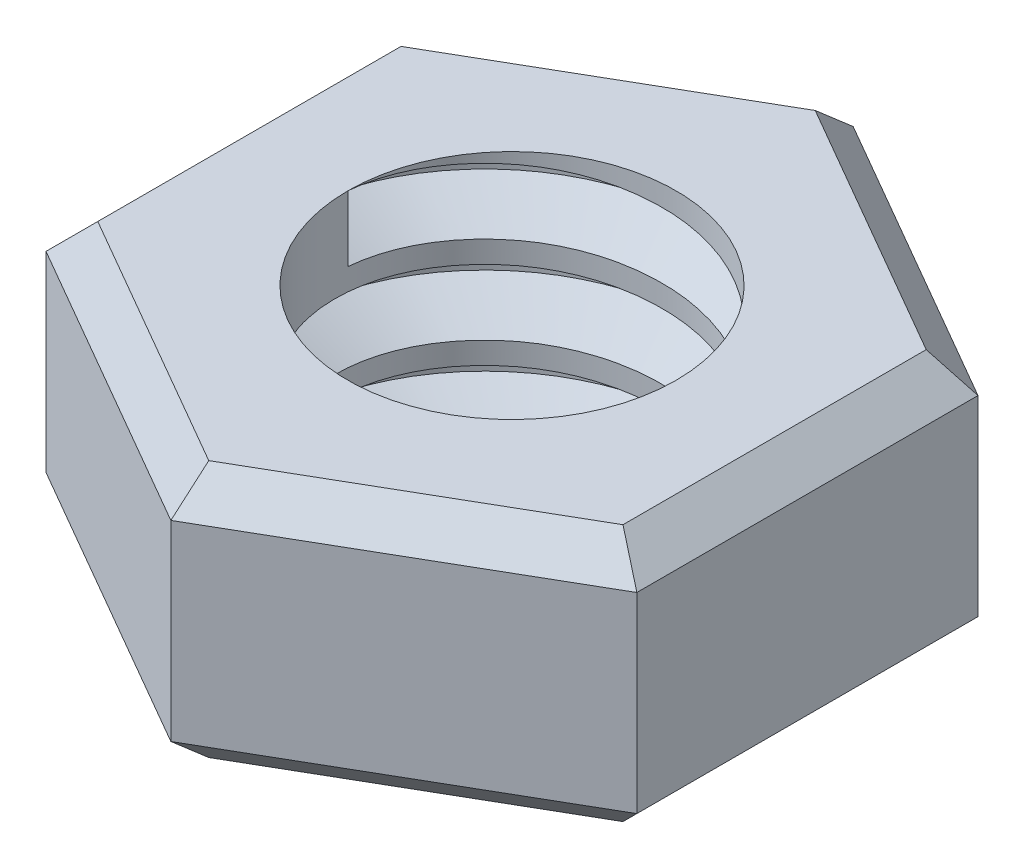
SolidWorks part; units mm, degrees
material "普通碳钢"
ref_plane "前视基准面" through (0, 0, 0) normal (0, 0, 1) x (1, 0, 0)
ref_plane "上视基准面" through (0, 0, 0) normal (0, 1, 0) x (1, 0, 0)
ref_plane "右视基准面" through (0, 0, 0) normal (1, 0, 0) x (0, 0, -1)
sketch "草图1" plane through (0, 0, 0) normal (0, 1, 0) x (1, 0, 0)
  line L1 (0, 3.1177) -> (-2.7, 1.5588)
  line L2 (-2.7, 1.5588) -> (-2.7, -1.5588)
  line L3 (-2.7, -1.5588) -> (0, -3.1177)
  line L4 (0, -3.1177) -> (2.7, -1.5588)
  line L5 (2.7, -1.5588) -> (2.7, 1.5588)
  line L6 (2.7, 1.5588) -> (0, 3.1177)
  circle A0 centre (0, 0) radius 2.7 construction
  circle A1 centre (0, 0) radius 1.5
  dimension "D2" = 3
  dimension "D1" = 5.4
extrude "凸台-拉伸1" add sketch "草图1" along normal blind 2.35
chamfer "倒角1" distance 0.3 angle 45 12 edges at (2.7, 2.35, 0) (1.35, 2.35, 2.3383) (-1.35, 2.35, 2.3383) (-2.7, 2.35, 0) (-1.35, 2.35, -2.3383) (1.35, 2.35, -2.3383) (-1.35, 0, -2.3383) (-2.7, 0, 0) (-1.35, 0, 2.3383) (1.35, 0, 2.3383) (2.7, 0, 0) (1.35, 0, -2.3383)
thread "螺纹线1" pitch 0.8 method cut profile "螺纹线轮廓1" start angle 0, offset 0, length 0, pitch 0.8, diameter 3
ref_plane "基准面1" through (-1.5, 2.35, 0) normal (0, 0, 1) x (-1, 0, 0)
sketch "螺纹线轮廓1" plane through (-1.5, 2.35, 0) normal (0, 0, 1) x (-1, 0, 0)
  line L0 (0, 0) -> (0, 0.8) construction
  line L1 (0, 0) -> (0.433, 0.25)
  line L2 (0.433, 0.25) -> (0.433, 0.35)
  line L3 (0.433, 0.35) -> (0, 0.6)
  line L4 (0.433, 0.3) -> (0, 0.3) construction
  line L11 (0, 0) -> (0, 0.6)
  point P2 (0, 0)
  dimension "Pitch" = 0.8
  dimension "Profile_Angle" = 60
  dimension "Profile_Land" = 0.1
  dimension "Profile_Height" = 0.433
